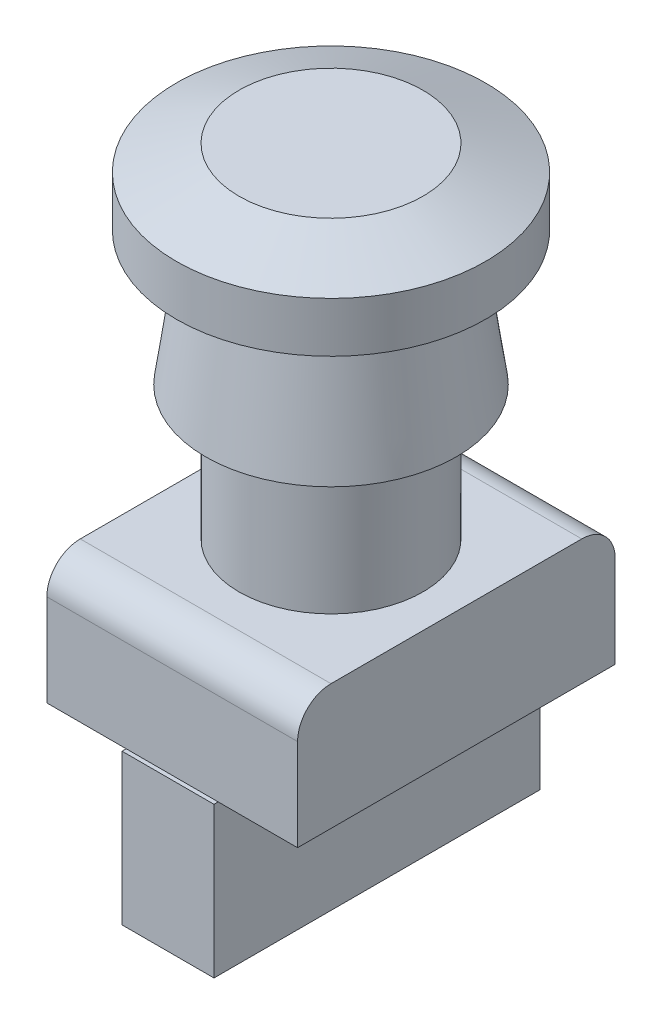
SolidWorks part; units mm, degrees
ref_plane "Płaszczyzna przednia" through (0, 0, 0) normal (0, 0, 1) x (1, 0, 0)
ref_plane "Płaszczyzna górna" through (0, 0, 0) normal (0, 1, 0) x (1, 0, 0)
ref_plane "Płaszczyzna prawa" through (0, 0, 0) normal (1, 0, 0) x (0, 0, -1)
sketch "Szkic1" plane through (0, 0, 0) normal (0, 1, 0) x (1, 0, 0)
  line L1 (-15, -19) -> (15, -19)
  line L2 (-15, -19) -> (-15, 19)
  line L3 (-15, 19) -> (15, 19)
  line L4 (15, -19) -> (15, 19)
  line L5 (-15, -19) -> (15, 19) construction
  line L6 (-15, 19) -> (15, -19) construction
  line L7 (-5.5, -19.5) -> (5.5, -19.5)
  line L8 (-5.5, -19.5) -> (-5.5, 19.5)
  line L9 (-5.5, 19.5) -> (5.5, 19.5)
  line L10 (5.5, -19.5) -> (5.5, 19.5)
  line L11 (-5.5, -19.5) -> (5.5, 19.5) construction
  line L12 (-5.5, 19.5) -> (5.5, -19.5) construction
  circle A0 centre (0, 0) radius 11
  circle A1 centre (0, 0) radius 15
  point P12 (5.5, 21.0449)
  dimension "D1" = 22
  dimension "D2" = 30
  dimension "D3" = 38
  dimension "D4" = 30
  dimension "D5" = 11
  dimension "D6" = 39
extrude "Dodanie-wyciągnięcie1" add sketch "Szkic1" along normal blind 15 draft 8 contours A1
extrude "Dodanie-wyciągnięcie2" add sketch "Szkic1<3>" against normal blind 16 contours A0
sketch "Szkic1<3>" plane through (0, 0, 0) normal (0, 1, 0) x (1, 0, 0) same geometry as "Szkic1"
extrude "Dodanie-wyciągnięcie3" add sketch "Szkic1<4>" against normal blind 15 from surface contours L3 L4 L1 L2 starting at face at (0, -16, 11)
sketch "Szkic1<4>" plane through (0, 0, 0) normal (0, 1, 0) x (1, 0, 0) same geometry as "Szkic1"
extrude "Dodanie-wyciągnięcie4" add sketch "Szkic1<5>" against normal blind 18 from surface contours L10 L9 L8 L7 starting at face at (0, -31, 0)
sketch "Szkic1<5>" plane through (0, 0, 0) normal (0, 1, 0) x (1, 0, 0) same geometry as "Szkic1"
sketch "Szkic2" plane through (0, 0, 0) normal (1, 0, 0) x (0, 0, -1)
  line L0 (0, 15) -> (0, 25)
  line L1 (12.8919, 15) -> (-12.8919, 15) construction
  line L2 (0, 25) -> (11, 25)
  line L3 (11, 25) -> (18.5, 22)
  line L4 (18.5, 22) -> (18.5, 16)
  line L5 (18.5, 16) -> (12, 16)
  line L6 (12, 16) -> (12, 15)
  line L7 (12, 15) -> (0, 15)
  line L8 (0, 34.0751) -> (0, -12.6218) construction
  dimension "D1" = 10
  dimension "D2" = 18.5
  dimension "D3" = 6
  dimension "D4" = 11
  dimension "D5" = 1
  dimension "D6" = 12
revolve "Obrót1" add sketch "Szkic2" angle 360 about L8
fillet "Zaokrąglenie1" radius 4 2 edges at (0, -16, 19) (0, -16, -19)
